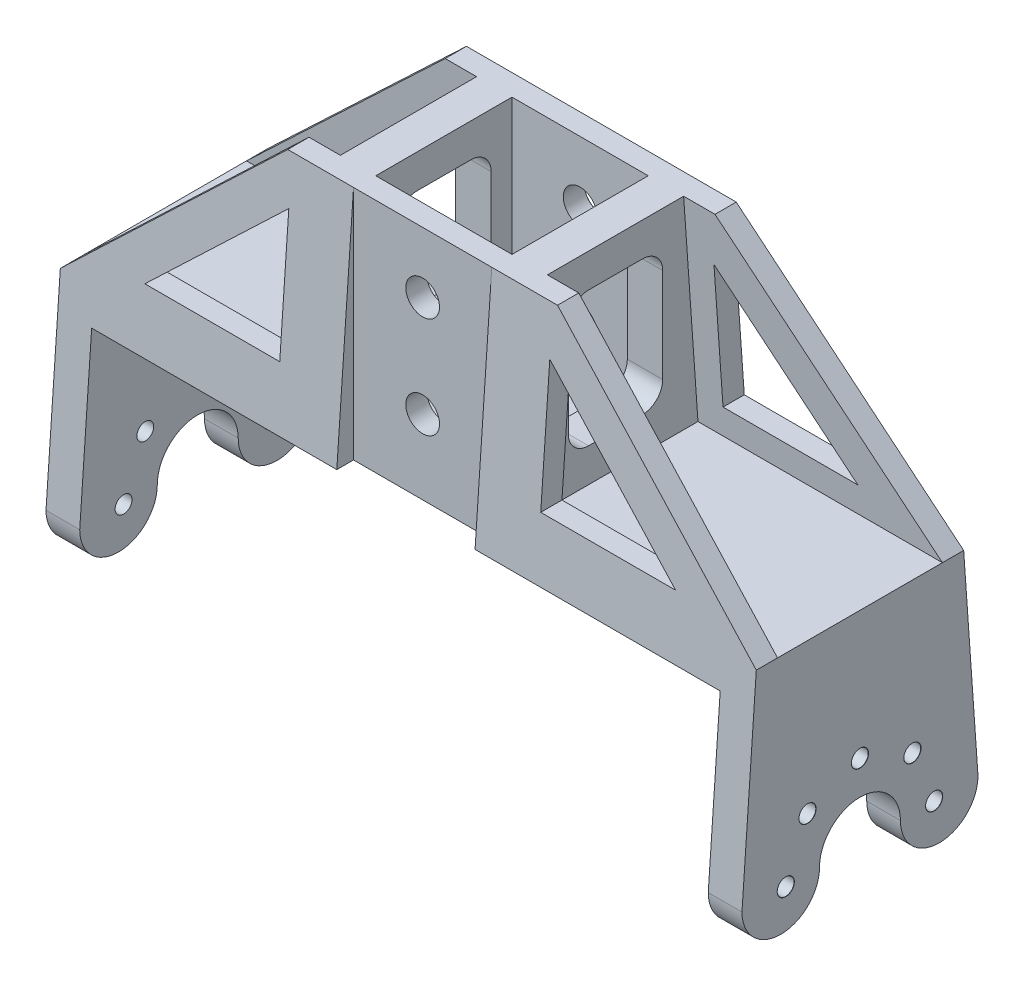
SolidWorks part; units mm, degrees
ref_plane "前视基准面" through (0, 0, 0) normal (0, 0, 1) x (1, 0, 0)
ref_plane "上视基准面" through (0, 0, 0) normal (0, 1, 0) x (1, 0, 0)
ref_plane "右视基准面" through (0, 0, 0) normal (1, 0, 0) x (0, 0, -1)
sketch "草图1" plane through (0, 0, 0) normal (0, 0, 1) x (1, 0, 0)
  line L0 (-2.4052, -0.0763) -> (-130.7806, -0.0763) construction
  line L1 (0, 0) -> (0, 37.5806) construction
  line L7 (51.6, -0.0763) -> (51.6, 29.9237)
  line L8 (51.6, 29.9237) -> (20, 59.9237)
  line L9 (20, 59.9237) -> (-20, 59.9237)
  line L10 (-20, 59.9237) -> (-51.6, 29.9237)
  line L11 (-51.6, 29.9237) -> (-51.6, -0.0763)
  line L12 (-51.6, -0.0763) -> (51.6, -0.0763)
  dimension "D1" = 103.2
  dimension "D2" = 60
  dimension "D5" = 30
  dimension "D6" = 40
extrude "凸台-拉伸1" add sketch "草图1" along normal blind 35
sketch "草图6" plane through (-51.6, 0, 0) normal (-1, 0, 0) x (0, 0, 1)
  line L0 (35, -0.0763) -> (0, -0.0763) construction
  circle A0 centre (17.5, -0.0763) radius 6
  dimension "D1" = 12
extrude "切除-拉伸2" cut sketch "草图6" against normal up to surface (103.2 mm away) up to face at (51.6, 14.9237, 17.5)
sketch "草图7" plane through (-51.6, 0, 0) normal (-1, 0, 0) x (0, 0, 1)
  line L0 (11.5, -0.0763) -> (0, -0.0763) construction
  line L1 (35, -0.0763) -> (23.5, -0.0763) construction
  circle A0 centre (5.75, -0.0763) radius 5.75
  circle A1 centre (29.25, -0.0763) radius 5.75
extrude "凸台-拉伸3" add sketch "草图7" against normal up to surface (103.2 mm away) up to face at (51.6, 10.9237, 17.5)
sketch "草图8" plane through (0, 0, 35) normal (0, 0, 1) x (1, 0, 0)
  line L0 (0, -0.0763) -> (0, 61.1377) construction
  line L2 (-46.6, -0.0763) -> (-46.6, 24.9237)
  line L3 (-51.6, -0.0763) -> (51.6, -0.0763) construction
  line L4 (-46.6, 24.9237) -> (46.6, 24.9237)
  line L5 (46.6, 24.9237) -> (46.6, -0.0763)
  line L7 (-46.6, -0.0763) -> (-46.6, -12.1113)
  line L8 (-46.6, -12.1113) -> (46.6, -12.1113)
  line L9 (46.6, -12.1113) -> (46.6, -0.0763)
  dimension "D1" = 93.2
  dimension "D2" = 25
extrude "切除-拉伸3" cut sketch "草图8" against normal up to surface (35 mm away) up to face at (0, 29.9237, 0)
hole_wizard "Ø2.5mm 暗销孔2" positions "草图12" profile "草图13" hole size "Ø2.5" standard "ISO" end condition through all
sketch "草图12" plane through (51.6, 0, 0) normal (1, 0, 0) x (0, 0, -1)
  line L0 (-17.5, 29.9237) -> (-17.5, -2.5018) construction
  line L3 (-29.25, -0.0763) -> (-5.5955, -0.0763) construction
  circle A1 centre (-17.5, -0.0763) radius 0.7969 construction
  point P44 (-28.5, -0.0763)
  point P72 (-25.2782, 7.7019)
  point P73 (-17.5, 10.9237)
  point P74 (-9.7218, 7.7019)
  point P75 (-6.5, -0.0763)
  dimension "D1" = 11
  dimension "D2" = 5
sketch "草图13" plane through (51.6, -0.0763, 28.5) normal (0, 1, 0) x (0, 0, -1)
  line L0 (0, 0) -> (0, 103.2)
  line L1 (0, 103.2) -> (1.25, 103.2)
  line L2 (1.25, 103.2) -> (1.25, 0.025)
  line L3 (1.25, 0.025) -> (1.275, 0)
  line L5 (1.275, 0) -> (0, 0)
  line L6 (-1.25, 0.025) -> (-1.275, 0) construction
  line L11 (0, -6.35) -> (0, 107.95) construction
  dimension "通孔孔直径" = 2.5
  dimension "通孔孔深度" = 103.2
  dimension "近端锥形沉头孔直径" = 2.55
  dimension "近端锥形沉头孔角度" = 90
sketch "草图16" plane through (0, 59.9237, 0) normal (0, 1, 0) x (1, 0, 0)
  line L0 (0, 0) -> (0, -35) construction
  line L3 (-20, -17.5) -> (20, -17.5) construction
  line L4 (-10.1, -7.4) -> (10.1, -7.4)
  line L5 (-10.1, -7.4) -> (-10.1, -27.6)
  line L6 (-10.1, -27.6) -> (10.1, -27.6)
  line L7 (10.1, -7.4) -> (10.1, -27.6)
  dimension "D1" = 20.2
  dimension "D2" = 20.2
extrude "切除-拉伸5" cut sketch "草图16" against normal blind 30
sketch "草图15" plane through (0, 0, 35) normal (0, 0, 1) x (1, 0, 0)
  line L0 (0, 24.9237) -> (0, 61.498) construction
  line L2 (0, 24.9237) -> (-10.25, 24.9237)
  line L3 (46.6, 24.9237) -> (-46.6, 24.9237) construction
  line L4 (-10.25, 24.9237) -> (-10.25, 59.9237)
  line L5 (20, 59.9237) -> (-20, 59.9237) construction
  line L6 (-10.25, 59.9237) -> (10.25, 59.9237)
  line L7 (10.25, 59.9237) -> (10.25, 24.9237)
  line L8 (10.25, 24.9237) -> (-10.25, 24.9237)
  dimension "D1" = 20.5
extrude "切除-拉伸6" cut sketch "草图15" against normal blind 4.25 contours L4 L6 L7 L8
sketch "草图17" plane through (0, 0, 0) normal (0, 0, -1) x (-1, 0, 0)
  line L4 (-10.25, 24.9237) -> (10.25, 24.9237)
  line L5 (-10.25, 59.9237) -> (-10.25, 24.9237)
  line L6 (10.25, 59.9237) -> (-10.25, 59.9237)
  line L7 (10.25, 24.9237) -> (10.25, 59.9237)
  line L8 (-10.25, 24.9237) -> (10.25, 24.9237)
  line L9 (-10.25, 59.9237) -> (-10.25, 24.9237)
  line L10 (10.25, 59.9237) -> (-10.25, 59.9237)
  line L11 (10.25, 24.9237) -> (10.25, 59.9237)
  dimension "D1" = 0
extrude "切除-拉伸7" cut sketch "草图17" against normal blind 4.25
hole_wizard "Ø5.0mm 暗销孔1" positions "草图18" profile "草图19" hole size "Ø5.0" standard "ISO" end condition through all
sketch "草图18" plane through (0, 0, 4.25) normal (0, 0, -1) x (-1, 0, 0)
  line L0 (0, 24.9237) -> (0, 65.7443) construction
  line L3 (0, 29.9237) -> (-37.1771, 29.9237) construction
  line L5 (-10.25, 24.9237) -> (10.25, 24.9237) construction
  point P18 (0, 35.9237)
  point P20 (0, 50.9237)
  dimension "D1" = 5
  dimension "D2" = 15
  dimension "D3" = 6
sketch "草图19" plane through (0, 50.9237, 4.25) normal (1, 0, 0) x (0, 1, 0)
  line L0 (0, 0) -> (0, 30.75)
  line L1 (0, 30.75) -> (2.5, 30.75)
  line L2 (2.5, 30.75) -> (2.5, 0.025)
  line L3 (2.5, 0.025) -> (2.525, 0)
  line L5 (2.525, 0) -> (0, 0)
  line L6 (-2.5, 0.025) -> (-2.525, 0) construction
  line L11 (0, -6.35) -> (0, 107.95) construction
  dimension "通孔孔直径" = 5
  dimension "通孔孔深度" = 30.75
  dimension "近端锥形沉头孔直径" = 5.05
  dimension "近端锥形沉头孔角度" = 90
sketch "草图20" plane through (51.6, 0, 0) normal (1, 0, 0) x (0, 0, -1)
  line L0 (-30.75, 59.9237) -> (-35, 59.9237) construction
  line L1 (-30.75, 59.9237) -> (-35, 59.9237)
  line L2 (-30.75, 59.9237) -> (-35, -0.0763)
  line L3 (-35, -0.0763) -> (-35, 59.9237)
  line L4 (-17.5, 59.9237) -> (-17.5, 49.5416) construction
  line L6 (0, -0.0763) -> (0, 59.9237)
  line L7 (-4.25, 59.9237) -> (0, -0.0763)
  line L8 (-4.25, 59.9237) -> (0, 59.9237)
extrude "切除-拉伸8" cut sketch "草图20" against normal up to surface (103.2 mm away) up to face at (-51.6, -0.0763, 27.25)
sketch "草图21" plane through (51.6, 0, 0) normal (1, 0, 0) x (0, 0, -1)
  line L0 (-27.6, 59.9237) -> (-29.725, 29.9237)
  line L1 (-17.5, 59.9237) -> (-17.5, 29.9237) construction
  line L3 (-32.875, 29.9237) -> (-2.125, 29.9237) construction
  line L4 (-29.725, 29.9237) -> (-5.275, 29.9237)
  line L5 (-27.6, 59.9237) -> (-7.4, 59.9237)
  line L6 (-30.75, 59.9237) -> (-4.25, 59.9237) construction
  line L7 (-7.4, 59.9237) -> (-5.275, 29.9237)
  line L8 (-30.75, 59.9237) -> (-32.875, 29.9237) construction
  point P10 (-17.5, 29.9237)
  point P11 (-17.5, 59.9237)
  dimension "D1" = 0
extrude "切除-拉伸9" cut sketch "草图21" against normal blind 36.25 contours L4 L7 L5 L0
sketch "草图22" plane through (-51.6, 0, 0) normal (-1, 0, 0) x (0, 0, 1)
  line L4 (29.725, 29.9237) -> (27.6, 59.9237)
  line L5 (5.275, 29.9237) -> (29.725, 29.9237)
  line L6 (7.4, 59.9237) -> (5.275, 29.9237)
  line L7 (27.6, 59.9237) -> (7.4, 59.9237)
  line L8 (29.725, 29.9237) -> (27.6, 59.9237)
  line L9 (5.275, 29.9237) -> (29.725, 29.9237)
  line L10 (7.4, 59.9237) -> (5.275, 29.9237)
  line L11 (27.6, 59.9237) -> (7.4, 59.9237)
  dimension "D1" = 0
extrude "切除-拉伸10" cut sketch "草图22" against normal blind 36.25
sketch "草图23" plane through (-15.35, 0, 0) normal (-1, 0, 0) x (0, 0, 1)
  line L0 (17.5, 59.9237) -> (17.5, 29.9237) construction
  line L3 (13.5, 34.9237) -> (21.5, 34.9237)
  line L4 (10.5, 37.9237) -> (10.5, 51.9237)
  line L5 (17.65, 44.9237) -> (-13.119, 44.9237) construction
  line L6 (5.275, 29.9237) -> (29.725, 29.9237) construction
  line L7 (13.5, 54.9237) -> (21.5, 54.9237)
  line L8 (24.5, 37.9237) -> (24.5, 51.9237)
  arc A0 (10.5, 37.9237) -> (13.5, 34.9237) centre (13.5, 37.9237) ccw
  arc A1 (10.5, 31.9237) -> (13.5, 34.9237) centre (13.5, 31.9237) cw
  arc A2 (10.5, 51.9237) -> (13.5, 54.9237) centre (13.5, 51.9237) cw
  arc A3 (24.5, 37.9237) -> (21.5, 34.9237) centre (21.5, 37.9237) cw
  arc A4 (24.5, 51.9237) -> (21.5, 54.9237) centre (21.5, 51.9237) ccw
  point P20 (10.5, 44.9237)
  point P21 (17.5, 34.9237)
  point P26 (17.5, 54.9237)
  dimension "D1" = 3
  dimension "D2" = 15
  dimension "D3" = 7
  dimension "D4" = 4
extrude "切除-拉伸11" cut sketch "草图23" against normal up to surface (30.7 mm away) contours L3 A3 L8 A4 L7 A2 L4 A0 up to face at (15.35, 44.9237, 17.5)
sketch "草图25" plane through (0, 0, 0) normal (0, 0, 1) x (1, 0, 0)
  line L0 (15.35, 59.9237) -> (20, 59.9237) construction
  line L1 (15.35, 59.9237) -> (15.35, 29.9237) construction
  line L2 (15.35, 29.9237) -> (51.6, 29.9237) construction
  line L3 (15.35, 59.9237) -> (20, 59.9237) construction
  line L4 (15.35, 59.9237) -> (15.35, 29.9237) construction
  line L5 (15.35, 29.9237) -> (51.6, 29.9237) construction
  line L6 (39.35, 33.9237) -> (19.35, 33.9237)
  line L7 (19.35, 33.9237) -> (19.35, 52.9111)
  line L8 (19.35, 52.9111) -> (39.35, 33.9237)
  line L9 (0, 59.9237) -> (0, 24.9237) construction
  line L10 (15.35, 29.9237) -> (51.6, 29.9237)
  line L11 (15.35, 59.9237) -> (15.35, 29.9237)
  line L12 (20, 59.9237) -> (15.35, 59.9237)
  line L13 (51.6, 29.9237) -> (20, 59.9237)
  line L14 (15.35, 29.9237) -> (51.6, 29.9237) construction
  line L15 (15.35, 59.9237) -> (15.35, 29.9237) construction
  line L16 (20, 59.9237) -> (15.35, 59.9237) construction
  line L17 (51.6, 29.9237) -> (20, 59.9237) construction
  line L18 (-19.35, 52.9111) -> (-39.35, 33.9237)
  line L19 (-19.35, 33.9237) -> (-19.35, 52.9111)
  line L20 (-39.35, 33.9237) -> (-19.35, 33.9237)
  dimension "D2" = 4
  dimension "D3" = 4
  dimension "D4" = 20
  dimension "D1" = 0
extrude "切除-拉伸12" cut sketch "草图25" along normal through all
